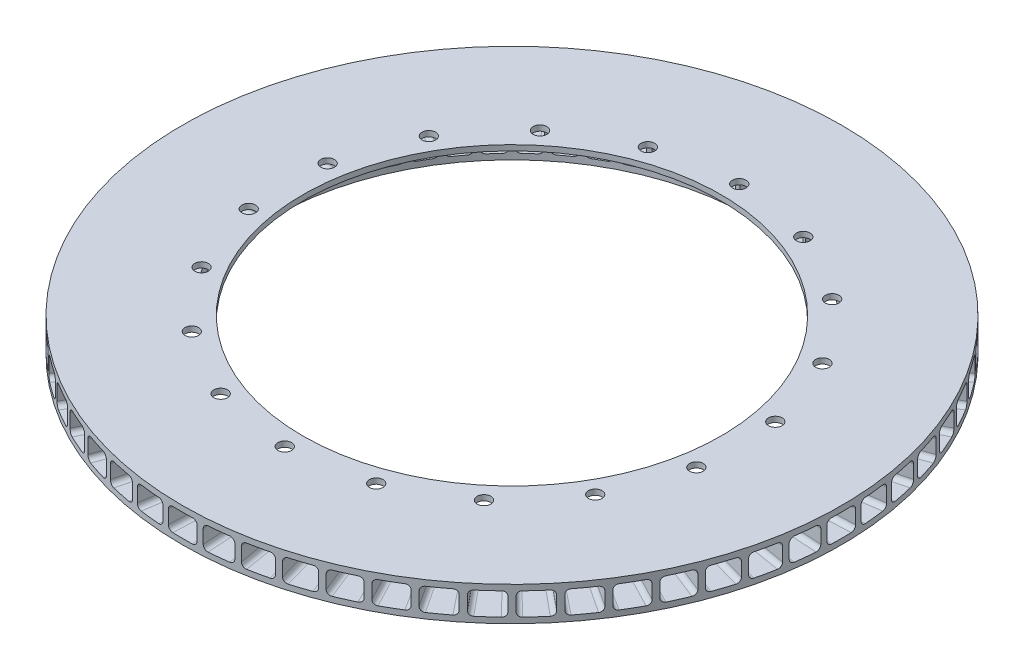
SolidWorks part; units mm, degrees
ref_plane "Front Plane" through (0, 0, 0) normal (0, 0, 1) x (1, 0, 0)
ref_plane "Top Plane" through (0, 0, 0) normal (0, 1, 0) x (1, 0, 0)
ref_plane "Right Plane" through (0, 0, 0) normal (1, 0, 0) x (0, 0, -1)
sketch "Sketch1" plane through (0, 0, 0) normal (0, 1, 0) x (1, 0, 0)
  line L0 (-124.462, -145) -> (124.462, -145) construction
  circle A0 centre (0, 0) radius 145
  point P6 (0, -145)
  dimension "D1" = 290
extrude "Boss-Extrude1" add sketch "Sketch1" along normal mid plane 15
sketch "Sketch2" plane through (0, 7.5, 0) normal (0, 1, 0) x (1, 0, 0)
  circle A0 centre (0, 0) radius 105
  dimension "D1" = 210
extrude "Cut-Extrude1" cut sketch "Sketch2" against normal up to next
sketch "Sketch3" plane through (0, 0, 0) normal (1, 0, 0) x (0, 0, -1)
  line L0 (159.5, 0) -> (-159.5, 0) construction
  line L1 (-149, 5) -> (-104, 5)
  line L2 (-149, 5) -> (-149, -5)
  line L3 (-149, -5) -> (-104, -5)
  line L4 (-104, 5) -> (-104, -5)
  line L5 (-149, 5) -> (-104, -5) construction
  line L6 (-149, -5) -> (-104, 5) construction
  line L7 (0, 40.2612) -> (0, -51.2505) construction
  point P0 (-126.5, 0)
  dimension "D1" = 45
  dimension "D2" = 10
  dimension "D3" = 104
revolve "Cut-Revolve1" cut sketch "Sketch3" angle 5 mid plane about L7
pattern_circular "CirPattern1" count 60 over 360 about axis through (0, 7.5, 0) along (0, 1, 0) of "Cut-Revolve1"
fillet "Fillet2" radius 2 240 edges at (-18.4762, 5, 123.627) (-7.6311, 5, 124.7668) (-7.6311, -5, 124.7668) (-18.4762, -5, 123.627) (-43.7759, 5, 117.084) (-33.4048, 5, 120.4538) (-33.4048, -5, 120.4538) (-43.7759, -5, 117.084) (-67.1625, 5, 105.4239) (-57.7186, 5, 110.8764) (-57.7186, -5, 110.8764) (-67.1625, -5, 105.4239) (-87.6137, 5, 89.1563) (-79.5098, 5, 96.4531) (-79.5098, -5, 96.4531) (-87.6137, -5, 89.1563) (-97.826, -5, 77.8143) (-104.2357, -5, 68.9921) (-116.3022, 5, 45.8127) (-111.8668, 5, 55.7747) (-111.8668, -5, 55.7747) (-116.3022, -5, 45.8127) (-123.2857, 5, 20.631) (-121.0185, 5, 31.2975) (-121.0185, -5, 31.2975) (-123.2857, -5, 20.631) (-124.881, 5, -5.4524) (-124.881, 5, 5.4524) (-124.881, -5, 5.4524) (-124.881, -5, -5.4524) (-121.0185, 5, -31.2975) (-123.2857, 5, -20.631) (-123.2857, -5, -20.631) (-121.0185, -5, -31.2975) (-111.8668, 5, -55.7747) (-116.3022, 5, -45.8127) (-116.3022, -5, -45.8127) (-111.8668, -5, -55.7747) (-97.826, 5, -77.8143) (-104.2357, 5, -68.9921) (-104.2357, -5, -68.9921) (-97.826, -5, -77.8143) (-79.5098, 5, -96.4531) (-87.6137, 5, -89.1563) (-87.6137, -5, -89.1563) (-79.5098, -5, -96.4531) (-57.7186, 5, -110.8764) (-67.1625, 5, -105.4239) (-67.1625, -5, -105.4239) (-57.7186, -5, -110.8764) (-33.4048, 5, -120.4538) (-43.7759, 5, -117.084) (-43.7759, -5, -117.084) (-33.4048, -5, -120.4538) (-7.6311, 5, -124.7668) (-18.4762, 5, -123.627) (-18.4762, -5, -123.627) (-7.6311, -5, -124.7668) (18.4762, 5, -123.627) (7.6311, 5, -124.7668) (7.6311, -5, -124.7668) (18.4762, -5, -123.627) (43.7759, 5, -117.084) (33.4048, 5, -120.4538) (33.4048, -5, -120.4538) (43.7759, -5, -117.084) (67.1625, 5, -105.4239) (57.7186, 5, -110.8764) (57.7186, -5, -110.8764) (67.1625, -5, -105.4239) (87.6137, 5, -89.1563) (79.5098, 5, -96.4531) (79.5098, -5, -96.4531) (87.6137, -5, -89.1563) (104.2357, 5, -68.9921) (97.826, 5, -77.8143) (97.826, -5, -77.8143) (104.2357, -5, -68.9921) (116.3022, 5, -45.8127) (111.8668, 5, -55.7747) (111.8668, -5, -55.7747) (116.3022, -5, -45.8127) (123.2857, 5, -20.631) (121.0185, 5, -31.2975) (121.0185, -5, -31.2975) (123.2857, -5, -20.631) (124.881, 5, 5.4524) (124.881, 5, -5.4524) (124.881, -5, -5.4524) (124.881, -5, 5.4524) (121.0185, 5, 31.2975) (123.2857, 5, 20.631) (123.2857, -5, 20.631) (121.0185, -5, 31.2975) (111.8668, 5, 55.7747) (116.3022, 5, 45.8127) (116.3022, -5, 45.8127) (111.8668, -5, 55.7747) (97.826, 5, 77.8143) (104.2357, 5, 68.9921) (104.2357, -5, 68.9921) (97.826, -5, 77.8143) (79.5098, 5, 96.4531) (87.6137, 5, 89.1563) (87.6137, -5, 89.1563) (79.5098, -5, 96.4531) (57.7186, 5, 110.8764) (67.1625, 5, 105.4239) (67.1625, -5, 105.4239) (57.7186, -5, 110.8764) (33.4048, 5, 120.4538) (43.7759, 5, 117.084) (43.7759, -5, 117.084) (33.4048, -5, 120.4538) (7.6311, 5, 124.7668) (18.4762, 5, 123.627) (18.4762, -5, 123.627) (7.6311, -5, 124.7668) (-5.4524, 5, 124.881) (5.4524, 5, 124.881) (5.4524, -5, 124.881) (-5.4524, -5, 124.881) (20.631, 5, 123.2857) (31.2975, 5, 121.0185) (31.2975, -5, 121.0185) (20.631, -5, 123.2857) (45.8127, 5, 116.3022) (55.7747, 5, 111.8668) (55.7747, -5, 111.8668) (45.8127, -5, 116.3022) (68.9921, 5, 104.2357) (77.8143, 5, 97.826) (77.8143, -5, 97.826) (68.9921, -5, 104.2357) (89.1563, 5, 87.6137) (96.4531, 5, 79.5098) (96.4531, -5, 79.5098) (89.1563, -5, 87.6137) (105.4239, 5, 67.1625) (110.8764, 5, 57.7186) (110.8764, -5, 57.7186) (105.4239, -5, 67.1625) (117.084, 5, 43.7759) (120.4538, 5, 33.4048) (120.4538, -5, 33.4048) (117.084, -5, 43.7759) (123.627, 5, 18.4762) (124.7668, 5, 7.6311) (124.7668, -5, 7.6311) (123.627, -5, 18.4762) (124.7668, 5, -7.6311) (123.627, 5, -18.4762) (123.627, -5, -18.4762) (124.7668, -5, -7.6311) (120.4538, 5, -33.4048) (117.084, 5, -43.7759) (117.084, -5, -43.7759) (120.4538, -5, -33.4048) (110.8764, 5, -57.7186) (105.4239, 5, -67.1625) (105.4239, -5, -67.1625) (110.8764, -5, -57.7186) (96.4531, 5, -79.5098) (89.1563, 5, -87.6137) (89.1563, -5, -87.6137) (96.4531, -5, -79.5098) (77.8143, 5, -97.826) (68.9921, 5, -104.2357) (68.9921, -5, -104.2357) (77.8143, -5, -97.826) (55.7747, 5, -111.8668) (45.8127, 5, -116.3022) (45.8127, -5, -116.3022) (55.7747, -5, -111.8668) (31.2975, 5, -121.0185) (20.631, 5, -123.2857) (20.631, -5, -123.2857) (31.2975, -5, -121.0185) (5.4524, 5, -124.881) (-5.4524, 5, -124.881) (-5.4524, -5, -124.881) (5.4524, -5, -124.881) (-20.631, 5, -123.2857) (-31.2975, 5, -121.0185) (-31.2975, -5, -121.0185) (-20.631, -5, -123.2857) (-45.8127, 5, -116.3022) (-55.7747, 5, -111.8668) (-55.7747, -5, -111.8668) (-45.8127, -5, -116.3022) (-68.9921, 5, -104.2357) (-77.8143, 5, -97.826) (-77.8143, -5, -97.826) (-68.9921, -5, -104.2357) (-89.1563, 5, -87.6137) (-96.4531, 5, -79.5098) (-96.4531, -5, -79.5098) (-89.1563, -5, -87.6137) (-105.4239, 5, -67.1625) (-110.8764, 5, -57.7186) (-110.8764, -5, -57.7186) (-105.4239, -5, -67.1625) (-117.084, 5, -43.7759) (-120.4538, 5, -33.4048) (-120.4538, -5, -33.4048) (-117.084, -5, -43.7759) (-123.627, 5, -18.4762) (-124.7668, 5, -7.6311) (-124.7668, -5, -7.6311) (-123.627, -5, -18.4762) (-124.7668, 5, 7.6311) (-123.627, 5, 18.4762) (-123.627, -5, 18.4762) (-124.7668, -5, 7.6311) (-120.4538, 5, 33.4048) (-117.084, 5, 43.7759) (-117.084, -5, 43.7759) (-120.4538, -5, 33.4048) (-110.8764, 5, 57.7186) (-105.4239, 5, 67.1625) (-105.4239, -5, 67.1625) (-110.8764, -5, 57.7186) (-96.4531, 5, 79.5098) (-89.1563, 5, 87.6137) (-89.1563, -5, 87.6137) (-96.4531, -5, 79.5098) (-77.8143, 5, 97.826) (-68.9921, 5, 104.2357) (-68.9921, -5, 104.2357) (-77.8143, -5, 97.826) (-55.7747, 5, 111.8668) (-45.8127, 5, 116.3022) (-45.8127, -5, 116.3022) (-55.7747, -5, 111.8668) (-31.2975, 5, 121.0185) (-20.631, 5, 123.2857) (-20.631, -5, 123.2857) (-31.2975, -5, 121.0185) (-97.826, 5, 77.8143) (-104.2357, 5, 68.9921)
ref_plane "Plane1" through (0, 7.5, 0) normal (0, 1, 0) x (1, 0, 0)
sketch "Sketch6" plane through (0, 7.5, 0) normal (0, 1, 0) x (1, 0, 0)
  circle A0 centre (0, 0) radius 105
  circle A1 centre (0, 0) radius 92
  dimension "D1" = 184
extrude "Boss-Extrude2" add sketch "Sketch6" against normal blind 2.4
sketch "Sketch7" plane through (0, 7.5, 0) normal (0, 1, 0) x (1, 0, 0)
  line L0 (0, 183.5321) -> (0, -219.5809) construction
  line L1 (178.1523, 0) -> (-182.2458, 0) construction
  circle A0 centre (0, 0) radius 100 construction
  circle A1 centre (0, 100) radius 3
  dimension "D1" = 200
  dimension "D2" = 6
extrude "Cut-Extrude2" cut sketch "Sketch7" against normal up to next
pattern_circular "CirPattern2" count 18 over 360 about axis through (0, 5.1, 0) along (0, 1, 0) of "Cut-Extrude2"
ref_plane "Plane2" through (0, 0, 145) normal (0, 0, 1) x (1, 0, 0)
